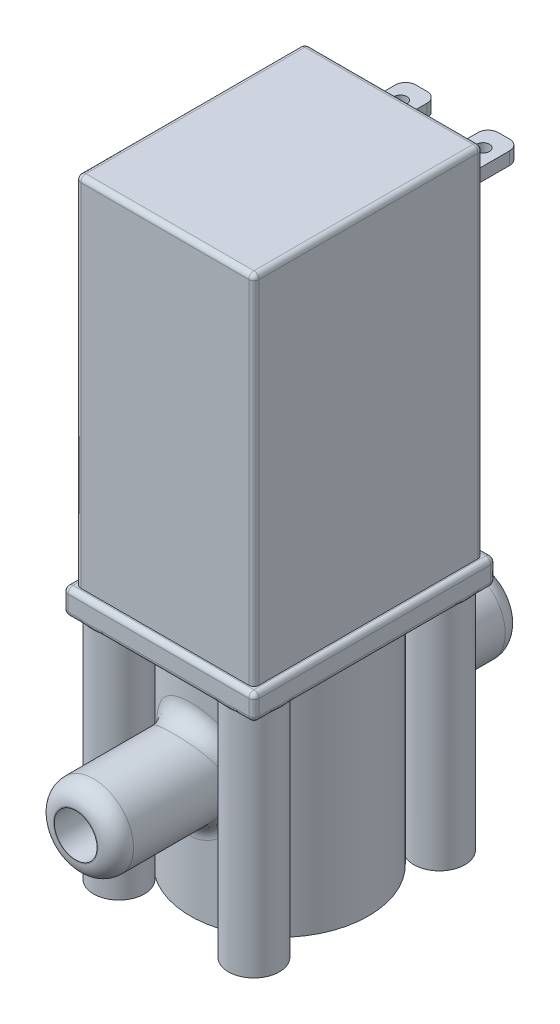
SolidWorks part; units mm, degrees
ref_plane "Front Plane" through (0, 0, 0) normal (0, 0, 1) x (1, 0, 0)
ref_plane "Top Plane" through (0, 0, 0) normal (0, 1, 0) x (1, 0, 0)
ref_plane "Right Plane" through (0, 0, 0) normal (1, 0, 0) x (0, 0, -1)
sketch "Sketch1" plane through (0, 0, 0) normal (0, 1, 0) x (1, 0, 0)
  line L1 (-12.11, 9.945) -> (5.67, 9.945)
  line L2 (-12.11, 9.945) -> (-12.11, -12.915)
  line L3 (-12.11, -12.915) -> (5.67, -12.915)
  line L4 (5.67, 9.945) -> (5.67, -12.915)
  dimension "D1" = 22.86
  dimension "D2" = 17.78
extrude "Boss-Extrude1" add sketch "Sketch1" along normal blind 60.96
ref_plane "Plane1" through (0, 25.4, 0) normal (0, -1, 0) x (-1, 0, 0)
sketch "Sketch2" plane through (0, 25.4, 0) normal (0, -1, 0) x (-1, 0, 0)
  line L0 (3.22, 10.58) -> (3.22, -13.55) construction
  line L1 (12.745, -13.55) -> (-6.305, -13.55)
  line L2 (12.745, -13.55) -> (12.745, 10.58)
  line L3 (12.745, 10.58) -> (-6.305, 10.58)
  line L4 (-6.305, -13.55) -> (-6.305, 10.58)
  line L5 (3.22, 9.945) -> (3.22, -12.915) construction
  line L6 (-5.67, 9.945) -> (12.11, 9.945) construction
  line L7 (12.11, -12.915) -> (-5.67, -12.915) construction
  line L8 (12.745, -1.485) -> (-6.305, -1.485) construction
  line L9 (12.11, -1.485) -> (-5.67, -1.485) construction
  line L10 (12.11, 9.945) -> (12.11, -12.915) construction
  line L11 (-5.67, -12.915) -> (-5.67, 9.945) construction
  dimension "D1" = 19.05
  dimension "D2" = 24.13
extrude "Boss-Extrude2" add sketch "Sketch2" along normal blind 2.54
sketch "Sketch3" plane through (0, 0, 0) normal (0, -1, 0) x (1, 0, 0)
  line L0 (-12.11, 12.915) -> (5.67, -9.945) construction
  line L1 (-12.11, -9.945) -> (5.67, 12.915) construction
  line L2 (-12.11, -9.945) -> (-12.11, 12.915) construction
  line L3 (-12.11, 1.485) -> (-12.11, 12.915)
  line L4 (-12.11, 12.915) -> (5.67, 12.915)
  line L5 (5.67, 12.915) -> (5.67, 1.485)
  circle A0 centre (-3.22, 1.485) radius 8.89
  point P12 (-3.22, 1.485)
  line M2 (-12.11, 12.915) -> (-12.11, -9.945)
  line M3 (-12.11, -9.945) -> (5.67, -9.945)
  line M4 (5.67, -9.945) -> (5.67, 12.915)
  line M5 (5.67, 12.915) -> (-12.11, 12.915)
extrude "Cut-Extrude2" cut sketch "Sketch3" against normal up to surface (22.86 mm away) contours A0 M4 M5 M2 | A0 M2 M3 M4 up to face at (-3.22, 22.86, 1.485)
sketch "Sketch5" plane through (0, 22.86, 0) normal (0, -1, 0) x (1, 0, 0)
  line L0 (-12.745, 13.55) -> (-12.745, -10.58) construction
  line L1 (6.305, 13.55) -> (-12.745, 13.55) construction
  line L2 (6.305, -10.58) -> (6.305, 13.55) construction
  circle A0 centre (-9.951, 10.756) radius 2.54
  circle A1 centre (-9.951, -7.7489) radius 2.54
  circle A2 centre (3.511, 10.756) radius 2.54
  circle A3 centre (3.511, -7.7489) radius 2.54
  circle A4 centre (-9.951, 10.756) radius 1.27
  circle A5 centre (3.511, 10.756) radius 1.27
  circle A6 centre (-9.951, -7.7489) radius 1.27
  circle A7 centre (3.511, -7.7489) radius 1.27
  dimension "D1" = 5.08
  dimension "D5" = 2.54
  dimension "D2" = 2.794
  dimension "D3" = 2.794
  dimension "D4" = 2.794
extrude "Boss-Extrude3" add sketch "Sketch5" along normal up to surface (22.86 mm away) up to face at (-3.22, 0, -7.405)
ref_plane "Plane2" through (0, 0, 1.485) normal (0, 0, 1) x (1, 0, 0)
sketch "Sketch6" plane through (0, 0, 1.485) normal (0, 0, 1) x (1, 0, 0)
  line L0 (-12.11, 60.96) -> (-12.11, 25.4) construction
  line L1 (-9.779, 25.4) -> (9.779, 25.4) construction
  circle A0 centre (-3.22, 12.7) radius 3.9921
  dimension "D1" = 8.89
  dimension "D2" = 12.7
extrude "Boss-Extrude4" add sketch "Sketch6" along normal blind 20.32 and the other way blind 20.32
sketch "Sketch7" plane through (0, 0, 21.805) normal (0, 0, 1) x (1, 0, 0)
  circle A0 centre (-3.22, 12.7) radius 2.1351
extrude "Cut-Extrude4" cut sketch "Sketch7" against normal blind 49.022
fillet "Fillet2" radius 1.778 2 edges at (-7.1793, 12.1892, 9.4447) (-3.7163, 8.7389, -7.3911)
fillet "Fillet3" radius 1.778 2 edges at (0.7721, 12.7, 21.805) (0.7721, 12.7, -18.835)
ref_plane "Plane3" through (0, 55.88, 0) normal (0, 1, 0) x (1, 0, 0)
sketch "Sketch8" plane through (0, 55.88, 0) normal (0, 1, 0) x (1, 0, 0)
  line L0 (-3.22, 9.945) -> (-3.22, -12.915) construction
  line L1 (-8.9161, 16.8033) -> (-5.76, 16.8033)
  line L2 (-8.9161, 16.8033) -> (-8.9161, 9.1833)
  line L3 (-8.9161, 9.1833) -> (-5.76, 9.1833)
  line L4 (-5.76, 16.8033) -> (-5.76, 9.1833)
  line L5 (-0.68, 16.8033) -> (2.4761, 16.8033)
  line L6 (-0.68, 16.8033) -> (-0.68, 9.1833)
  line L7 (-0.68, 9.1833) -> (2.4761, 9.1833)
  line L8 (2.4761, 16.8033) -> (2.4761, 9.1833)
  line L9 (-12.11, 9.945) -> (5.67, 9.945) construction
  line L10 (5.67, -12.915) -> (-12.11, -12.915) construction
  circle A0 centre (-7.338, 14.718) radius 0.635
  circle A1 centre (0.898, 14.718) radius 0.635
  dimension "D4" = 1.27
  dimension "D1" = 2.54
  dimension "D2" = 2.54
  dimension "D3" = 7.62
extrude "Boss-Extrude6" add sketch "Sketch8" against normal blind 1.27
fillet "Fillet4" radius 1.016 4 edges at (-8.9161, 55.245, -16.8033) (-5.76, 55.245, -16.8033) (-0.68, 55.245, -16.8033) (2.4761, 55.245, -16.8033)
fillet "Fillet5" radius 0.508 4 edges at (-3.22, 60.96, -9.945) (-12.11, 60.96, 1.485) (5.67, 60.96, 1.485) (-3.22, 60.96, 12.915)
fillet "Fillet6" radius 0.508 12 edges at (-12.745, 24.13, -10.58) (-3.22, 22.86, -10.58) (6.305, 24.13, -10.58) (-3.22, 25.4, -10.58) (6.305, 24.13, 13.55) (-3.22, 22.86, 13.55) (-12.745, 24.13, 13.55) (-3.22, 25.4, 13.55) (6.305, 25.4, 1.485) (-12.745, 25.4, 1.485) (-12.745, 22.86, 1.485) (6.305, 22.86, 1.485)
fillet "Fillet8" radius 0.508 8 edges at (5.5212, 60.8112, 12.7662) (-11.9612, 60.8112, 12.7662) (5.5212, 60.8112, -9.7962) (-11.9612, 60.8112, -9.7962) (5.67, 42.926, 12.915) (-12.11, 42.926, 12.915) (5.67, 42.926, -9.945) (-12.11, 42.926, -9.945)
